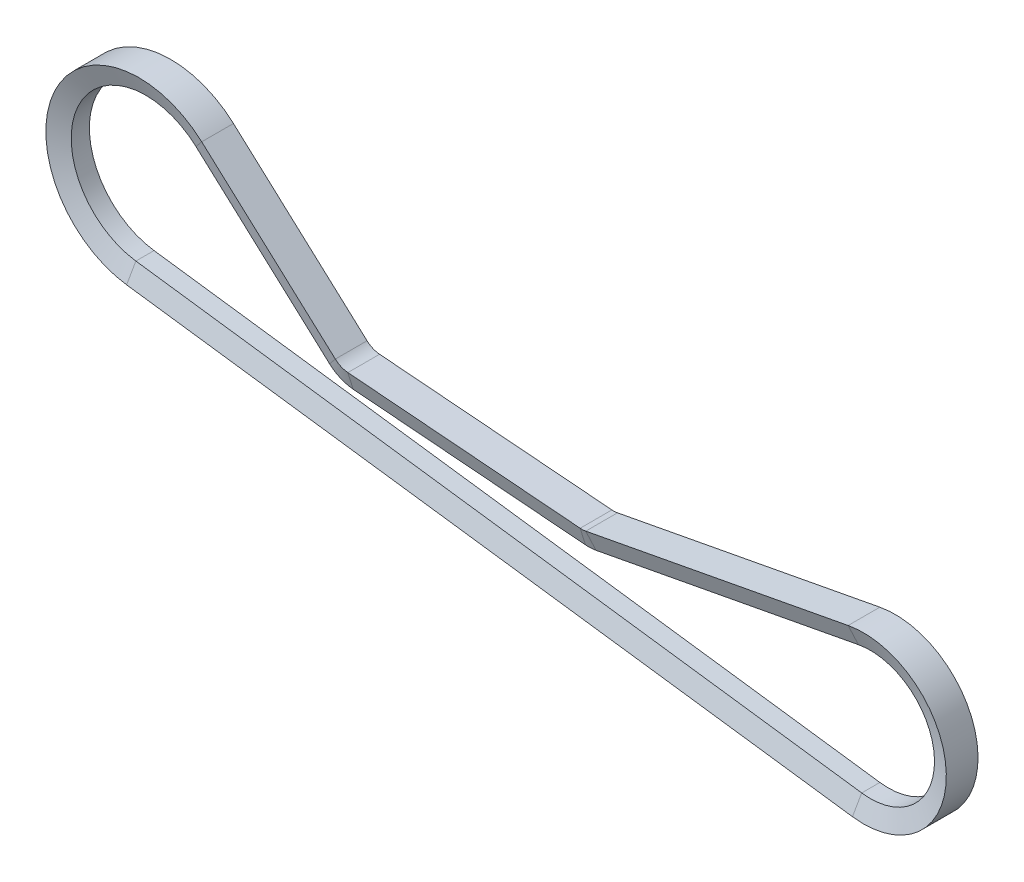
SolidWorks part; units mm, degrees
ref_plane "Front Plane" through (0, 0, 0) normal (0, 0, 1) x (1, 0, 0)
ref_plane "Top Plane" through (0, 0, 0) normal (0, 1, 0) x (1, 0, 0)
ref_plane "Right Plane" through (0, 0, 0) normal (1, 0, 0) x (0, 0, -1)
sketch "Sketch2" plane through (0, 0, 0) normal (0, 0, 1) x (1, 0, 0)
  line L0 (0, 0) -> (1, 0) construction
  line L1 (0, 0) -> (0, 1) construction
  line L12 (-3.3184, -24.6527) -> (-221.33, 4.6935)
  line L14 (-198.7721, 53.1727) -> (-158.6353, 16.7281)
  line L15 (-154.875, 15.0996) -> (-85.0998, 9.4946)
  line L16 (-83.4147, 9.5842) -> (-4.6094, 24.4442)
  arc A4 (-221.33, 4.6935) -> (-198.7721, 53.1727) centre (-217.5947, 32.4432) cw
  arc A7 (-4.6094, 24.4442) -> (-3.3184, -24.6527) centre (0, 0) cw
  arc A8 (-158.6353, 16.7281) -> (-154.875, 15.0996) centre (-154.3666, 21.4292) ccw
  arc A9 (-85.0998, 9.4946) -> (-83.4147, 9.5842) centre (-84.5914, 15.8242) ccw
ref_plane "Plane4" through (-4.6094, 24.4442, 0) normal (0.9827, 0.1853, 0) x (0.1853, -0.9827, 0)
sketch "Sketch3" plane through (-4.6094, 24.4442, 0) normal (0.9827, 0.1853, 0) x (0.1853, -0.9827, 0)
  line L0 (0, -4.7625) -> (0, 4.7625)
  line L1 (0, -4.7625) -> (5.588, -2.7286)
  line L2 (5.588, -2.7286) -> (5.588, 2.7286)
  line L3 (5.588, 2.7286) -> (0, 4.7625)
  line L4 (0, 0) -> (5.588, 0) construction
  dimension "D1" = 9.525
  dimension "D2" = 5.588
  dimension "D3" = 40
sweep "Sweep1" add profiles "Sketch3" path "Sketch2"
